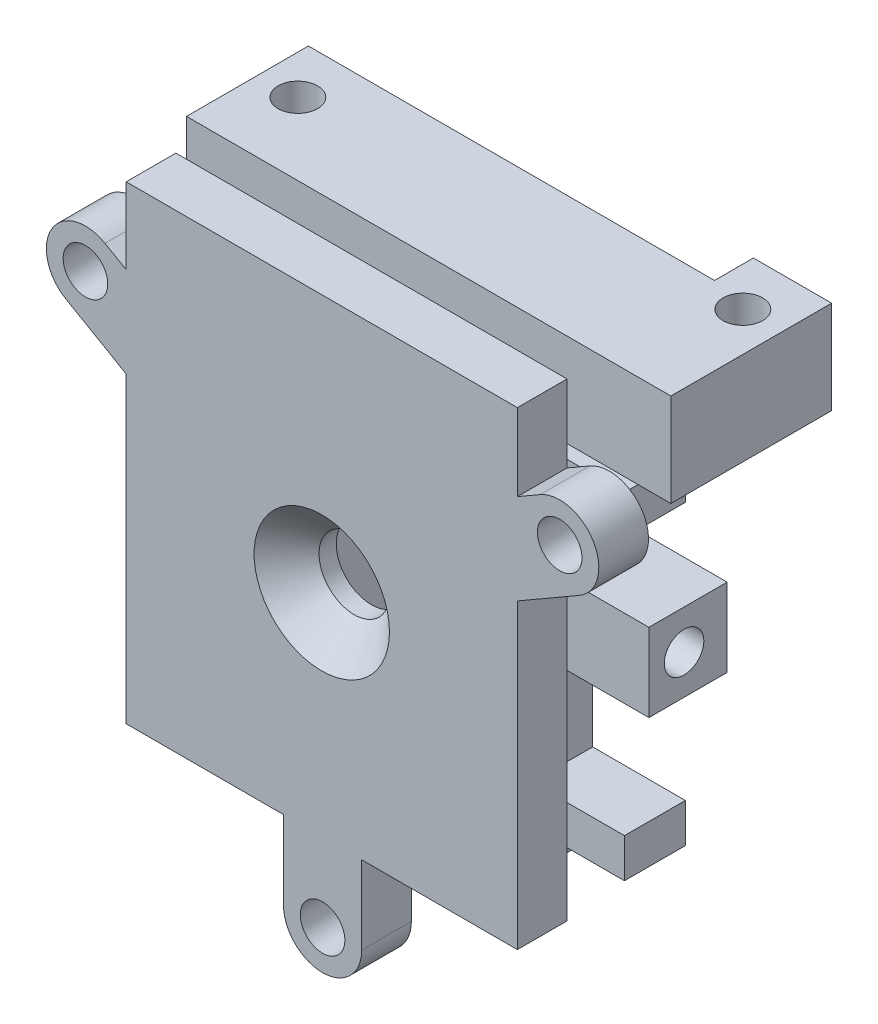
SolidWorks part; units mm, degrees
ref_plane "Front Plane" through (0, 0, 0) normal (0, 0, 1) x (1, 0, 0)
ref_plane "Top Plane" through (0, 0, 0) normal (0, 1, 0) x (1, 0, 0)
ref_plane "Right Plane" through (0, 0, 0) normal (1, 0, 0) x (0, 0, -1)
sketch "Sketch1" plane through (0, 0, 0) normal (0, 0, 1) x (1, 0, 0)
  line L5 (-5, 30) -> (5, 30)
  line L6 (-25, 30) -> (-5, 30)
  line L13 (-25, -30) -> (-4.8977, -30)
  line L31 (5.1023, -30) -> (25, -30)
  line L37 (-4.8977, -30) -> (-4.8977, -40)
  line L39 (5.1023, -30) -> (5.1023, -40)
  line L40 (0.1023, 0) -> (0.1023, -12.7655) construction
  line L41 (0.1023, 0) -> (-30.2086, 17.5) construction
  line L42 (0.1023, 0) -> (30.4132, 17.5) construction
  line L45 (5, 30) -> (25, 30)
  line L61 (25, 30) -> (25, 20.1482)
  line L62 (-25, 30) -> (-25, 20.2663)
  line L63 (-25, 8.7193) -> (-25, -30)
  line L65 (-27.7086, 21.8301) -> (-25, 20.2663)
  line L66 (-32.7086, 13.1699) -> (-25, 8.7193)
  line L67 (27.9132, 21.8301) -> (25, 20.1482)
  line L68 (32.9132, 13.1699) -> (25, 8.6012)
  line L69 (25, 8.6012) -> (25, -30)
  arc A20 (-4.8977, -40) -> (5.1023, -40) centre (0.1023, -40) ccw
  circle A21 centre (0.1023, -40) radius 2.85
  circle A22 centre (30.4132, 17.5) radius 2.85
  circle A23 centre (-30.2086, 17.5) radius 2.85
  arc A29 (-27.7086, 21.8301) -> (-32.7086, 13.1699) centre (-30.2086, 17.5) ccw
  arc A30 (32.9132, 13.1699) -> (27.9132, 21.8301) centre (30.4132, 17.5) ccw
  dimension "D1" = 50
  dimension "D2" = 60
  dimension "D3" = 25
  dimension "D7" = 30
  dimension "D5" = 10
  dimension "D6" = 10
  dimension "D9" = 5
  dimension "D10" = 5.7
  dimension "D11" = 120
  dimension "D12" = 120
  dimension "D13" = 25.1023
  dimension "D15" = 30.3109
  dimension "D14" = 10
  dimension "D17" = 10
  dimension "D16" = 8.9012
  dimension "D4" = 10
  dimension "D8" = 5
  dimension "D18" = 26.4769
  dimension "D19" = 32.1827
  dimension "D20" = 2.7086
  dimension "D21" = 26.4382
  dimension "D22" = 7.9132
  dimension "D23" = 32.1084
  dimension "D24" = 2.9132
extrude "Boss-Extrude1" add sketch "Sketch1" along normal blind 6.35
sketch "Sketch2" plane through (0, 0, 0) normal (0, 0, -1) x (-1, 0, 0)
  line L0 (-12.7, 34.75) -> (12.7, 34.75)
  line L2 (-12.7, 34.75) -> (-12.7, -34.75)
  line L3 (-12.7, -34.75) -> (12.7, -34.75)
  line L4 (12.7, 34.75) -> (12.7, -34.75)
  line L5 (-7.35, 23.4) -> (7.35, 23.4)
  line L6 (-7.35, 23.4) -> (-7.35, -29.4)
  line L7 (-7.35, -29.4) -> (7.35, -29.4)
  line L8 (7.35, 23.4) -> (7.35, -29.4)
  point P8 (-12.7, 0)
  point P13 (0, -34.75)
  dimension "D3" = 14.7
  dimension "D1" = 69.5
  dimension "D2" = 25.4
  dimension "D4" = 5.35
  dimension "D5" = 5.35
  dimension "D6" = 52.8
extrude "Boss-Extrude2" add sketch "Sketch2" along normal blind 15.5784
hole_wizard "CSK for M8 Flat Head Machine Screw1" positions "Sketch3" profile "Sketch4" countersink size "M8" standard "ANSI Metric"
sketch "Sketch3" plane through (0, 0, 6.35) normal (0, 0, 1) x (1, 0, 0)
  point P5 (0, -3)
  dimension "D1" = 3
sketch "Sketch4" plane through (0, -3, 6.35) normal (1, 0, 0) x (0, -1, 0)
  line L0 (0, 0) -> (0, 20.2039)
  line L1 (0, 20.2039) -> (4.5, 17.5)
  line L2 (4.5, 17.5) -> (4.5, 4.15)
  line L3 (4.5, 4.15) -> (8.65, 0)
  line L5 (8.65, 0) -> (0, 0)
  line L6 (-4.5, 4.15) -> (-8.65, 0) construction
  line L10 (0, 20.2039) -> (-4.5, 17.5) construction
  line L11 (0, -6.35) -> (0, 107.95) construction
  dimension "Hole Dia." = 9
  dimension "Hole Depth" = 17.5
  dimension "Near C'Sink Dia." = 17.3
  dimension "Near C'Sink Angle" = 90
  dimension "Drill Angle" = 118
sketch "Sketch6" plane through (12.7, 0, 0) normal (1, 0, 0) x (0, 0, -1)
  line L0 (15.5784, 34.75) -> (15.5784, -34.75) construction
  line L1 (0, 34.75) -> (15.5784, 34.75)
  line L2 (0, 34.75) -> (0, 22.85)
  line L3 (0, 22.85) -> (15.5784, 22.85)
  line L4 (15.5784, 34.75) -> (15.5784, 22.85)
  dimension "D1" = 11.9
extrude "Boss-Extrude3" add sketch "Sketch6" along normal blind 25.5721
sketch "Sketch7" plane through (-12.7, 0, 0) normal (-1, 0, 0) x (0, 0, 1)
  line L1 (-15.5784, 34.75) -> (0, 34.75)
  line L2 (-15.5784, 34.75) -> (-15.5784, 22.85)
  line L3 (-15.5784, 22.85) -> (0, 22.85)
  line L4 (0, 34.75) -> (0, 22.85)
  dimension "D1" = 11.9
extrude "Boss-Extrude4" add sketch "Sketch7" along normal blind 10.9373
sketch "Sketch8" plane through (0, 34.75, 0) normal (0, 1, 0) x (1, 0, 0)
  line L1 (-23.6373, 0) -> (-23.6373, 15.5784) construction
  line L3 (-23.6373, 15.5784) -> (38.2721, 15.5784) construction
  circle A0 centre (-18.6373, 9.2284) radius 2.5273
  dimension "D1" = 5.0546
  dimension "D2" = 6.35
  dimension "D3" = 5
extrude "Cut-Extrude1" cut sketch "Sketch8" against normal blind 7
sketch "Sketch9" plane through (0, 0, -15.5784) normal (0, 0, -1) x (-1, 0, 0)
  line L1 (-38.2721, 34.75) -> (-28.2721, 34.75)
  line L2 (-38.2721, 34.75) -> (-38.2721, 22.85)
  line L3 (-38.2721, 22.85) -> (-28.2721, 22.85)
  line L4 (-28.2721, 34.75) -> (-28.2721, 22.85)
  dimension "D1" = 10
extrude "Boss-Extrude5" add sketch "Sketch9" along normal blind 4.9727
sketch "Sketch10" plane through (0, 34.75, 0) normal (0, 1, 0) x (1, 0, 0)
  line L0 (38.2721, 20.5511) -> (38.2721, 0) construction
  line L1 (28.2721, 20.5511) -> (38.2721, 20.5511) construction
  circle A0 centre (33.2721, 14.2011) radius 2.5273
  circle A1 centre (-18.6373, 9.2284) radius 2.5273 construction
  dimension "D1" = 5
  dimension "D2" = 6.35
extrude "Cut-Extrude2" cut sketch "Sketch10" against normal blind 7
sketch "Sketch11" plane through (12.7, 0, 0) normal (1, 0, 0) x (0, 0, -1)
  line L0 (15.5784, 22.85) -> (15.5784, -34.75) construction
  line L1 (15.5784, -3.175) -> (20.9169, -3.175)
  line L2 (15.5784, -3.175) -> (15.5784, -13.175)
  line L3 (15.5784, -13.175) -> (20.9169, -13.175)
  line L4 (20.9169, -3.175) -> (20.9169, -13.175)
  line L5 (0, 22.85) -> (20.5511, 22.85) construction
  dimension "D1" = 26.025
  dimension "D2" = 10
  dimension "D3" = 5.3384
extrude "Boss-Extrude6" add sketch "Sketch11" against normal up to surface (5.35 mm away) up to face at (7.35, -3, -7.7892)
sketch "Sketch12" plane through (12.7, 0, 0) normal (1, 0, 0) x (0, 0, -1)
  line L0 (15.5784, -13.175) -> (20.9169, -13.175) construction
  line L1 (20.9169, -3.175) -> (10.9169, -3.175)
  line L2 (20.9169, -3.175) -> (20.9169, -13.175)
  line L3 (20.9169, -13.175) -> (10.9169, -13.175)
  line L4 (10.9169, -3.175) -> (10.9169, -13.175)
  line L5 (15.5784, 22.85) -> (15.5784, -3.175) construction
  line L6 (15.5784, 13.325) -> (7.7892, 13.325)
  line L7 (15.5784, 13.325) -> (15.5784, 8.325)
  line L8 (15.5784, 8.325) -> (7.7892, 8.325)
  line L9 (7.7892, 13.325) -> (7.7892, 8.325)
  line L10 (15.5784, -13.175) -> (15.5784, -34.75) construction
  line L11 (15.5784, -24.675) -> (7.7892, -24.675)
  line L12 (15.5784, -24.675) -> (15.5784, -29.675)
  line L13 (15.5784, -29.675) -> (7.7892, -29.675)
  line L14 (7.7892, -24.675) -> (7.7892, -29.675)
  point P13 (20.9169, -8.175)
  dimension "D1" = 10
  dimension "D2" = 21.5
  dimension "D3" = 7.7892
  dimension "D4" = 5
  dimension "D5" = 43
  dimension "D6" = 5
extrude "Boss-Extrude7" add sketch "Sketch12" along normal blind 11.85
sketch "Sketch13" plane through (24.55, 0, 0) normal (1, 0, 0) x (0, 0, -1)
  line L0 (10.9169, -3.175) -> (10.9169, -13.175) construction
  line L1 (10.9169, -13.175) -> (20.9169, -13.175) construction
  circle A0 centre (15.4092, -8.175) radius 2.5273
  dimension "D1" = 4.4924
  dimension "D3" = 5.0546
  dimension "D2" = 5
extrude "Cut-Extrude3" cut sketch "Sketch13" against normal blind 7
sketch "Sketch14" plane through (0, 0, -20.9169) normal (0, 0, -1) x (-1, 0, 0)
  line L6 (-12.7, -3.175) -> (-7.35, -3.175)
  line L7 (-12.7, -3.175) -> (-12.7, -13.175)
  line L8 (-12.7, -13.175) -> (-7.35, -13.175)
  line L9 (-7.35, -3.175) -> (-7.35, -13.175)
extrude "Cut-Extrude4" cut sketch "Sketch14" against normal up to surface (5.3384 mm away) up to face at (8.2654, -0.7792, -15.5784)
